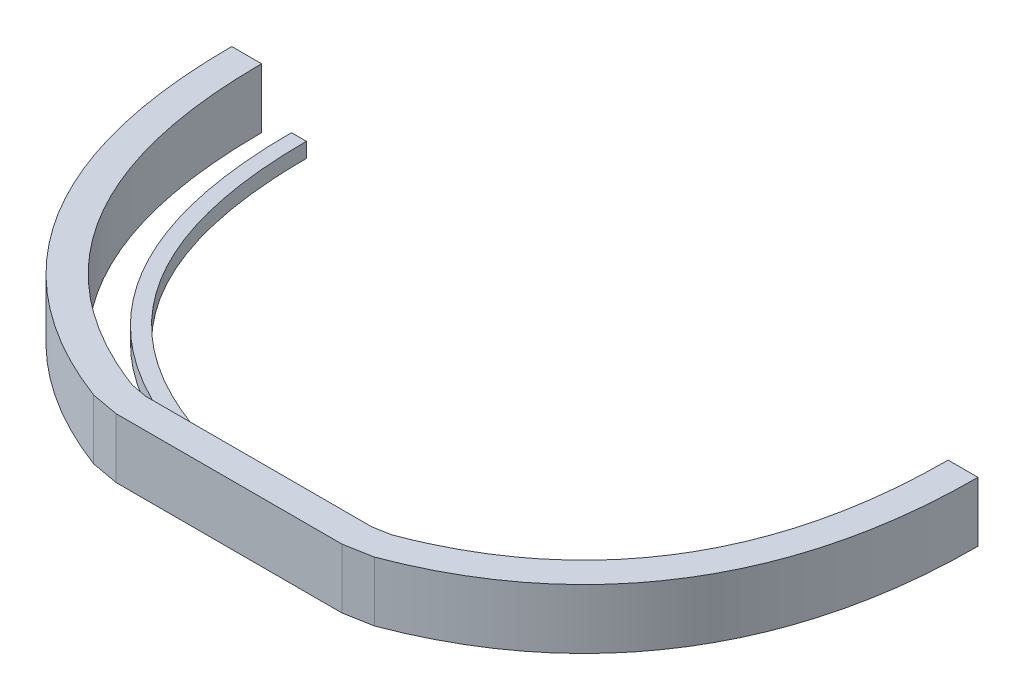
SolidWorks part; units mm, degrees
ref_plane "Front Plane" through (0, 0, 0) normal (0, 0, 1) x (1, 0, 0)
ref_plane "Top Plane" through (0, 0, 0) normal (0, 1, 0) x (1, 0, 0)
ref_plane "Right Plane" through (0, 0, 0) normal (1, 0, 0) x (0, 0, -1)
sketch "Sketch4" plane through (0, 0, -270) normal (0, 1, 0) x (-1, 0, 0)
  line L0 (137.8645, 275) -> (139.9706, 274.6182)
  line L1 (215, 169.1043) -> (225, 169.1044)
  line L2 (-25, 169.1044) -> (-15, 169.1043)
  line L3 (60.0294, 274.6182) -> (62.1355, 275)
  line L5 (62.1355, 285) -> (137.8645, 285)
  line L6 (56.5193, 283.9819) -> (62.1355, 285)
  line L7 (137.8645, 285) -> (143.4807, 283.9819)
  line L8 (62.1355, 275) -> (137.8645, 275)
  line L11 (62.1355, 295) -> (137.8645, 295)
  line L12 (53.0091, 293.3456) -> (62.1355, 295)
  line L13 (-5, 169.1042) -> (0, 169.1041)
  line L14 (137.8645, 295) -> (146.9909, 293.3456)
  line L15 (205, 169.1042) -> (200, 169.1041)
  line L16 (137.8645, 270) -> (138.2155, 269.9364)
  line L17 (61.7845, 269.9364) -> (62.1355, 270)
  line L18 (115.9492, 333.4763) -> (116.336, 333.6697)
  line L19 (62.1355, 270) -> (137.8645, 270)
  line L20 (62.1355, 270) -> (137.8645, 270)
  line L21 (62.1355, 275) -> (137.8645, 275)
  parabola Q8 (200, 169.1041) -> (138.2155, 269.9364) focus (145.0933, 217.5463) apex (175.9662, 244.7858) construction
  parabola Q9 (0, 169.1041) -> (61.7845, 269.9364) focus (54.9067, 217.5463) apex (24.0338, 244.7858) construction
  parabola Q10 (200, 169.1041) -> (138.2155, 269.9364) focus (145.0933, 217.5463) apex (175.9662, 244.7858)
  parabola Q11 (0, 169.1041) -> (61.7845, 269.9364) focus (54.9067, 217.5463) apex (24.0338, 244.7858)
  spline S0 degree 1 poles (-15, 169.1043) (56.5193, 283.9819) knots 0 0 1 1 construction
  spline S1 degree 3 poles (-15, 169.1043) (-15, 170.8319) (-14.9566, 174.3083) (-14.695, 181.0878) (-14.0365, 189.3567) (-12.7038, 198.9137) (-10.1854, 211.1772) (-5.6114, 225.5867) (2.2569, 241.2852) (12.5243, 255.1826) (22.9875, 265.0772) (32.3998, 271.9156) (39.9513, 276.5025) (46.6394, 279.8772) (52.2064, 282.3083) (55.0795, 283.4422) (56.5193, 283.9819) knots 0.497169 0.497169 0.497169 0.497169 0.497311 0.497453 0.497737 0.49802 0.498304 0.498871 0.499439 0.500006 0.500573 0.500857 0.501141 0.501424 0.501566 0.501708 0.501708 0.501708 0.501708
  spline S2 degree 1 poles (215, 169.1043) (143.4807, 283.9819) knots 0 0 1 1 construction
  spline S3 degree 3 poles (215, 169.1043) (215, 170.8319) (214.9566, 174.3083) (214.695, 181.0878) (214.0365, 189.3567) (212.7038, 198.9137) (210.1854, 211.1772) (205.6114, 225.5867) (197.7431, 241.2852) (187.4757, 255.1826) (177.0125, 265.0772) (167.6002, 271.9156) (160.0487, 276.5025) (153.3606, 279.8772) (147.7936, 282.3083) (144.9205, 283.4422) (143.4807, 283.9819) knots 0.497169 0.497169 0.497169 0.497169 0.497311 0.497453 0.497737 0.49802 0.498304 0.498871 0.499439 0.500006 0.500573 0.500857 0.501141 0.501424 0.501566 0.501708 0.501708 0.501708 0.501708
  spline S4 degree 1 poles (-25, 169.1044) (53.0091, 293.3456) knots 0 0 1 1 construction
  spline S5 degree 3 poles (-25, 169.1044) (-25, 170.9167) (-24.9546, 174.5598) (-24.6794, 181.6941) (-23.9842, 190.4326) (-22.5676, 200.5993) (-19.8721, 213.7329) (-14.9305, 229.327) (-6.3218, 246.5207) (4.9983, 261.8482) (16.5376, 272.7565) (26.8613, 280.2554) (35.1038, 285.2608) (42.3596, 288.921) (48.3721, 291.5462) (51.4599, 292.7649) (53.0091, 293.3456) knots 0.497169 0.497169 0.497169 0.497169 0.497311 0.497453 0.497737 0.49802 0.498304 0.498871 0.499439 0.500006 0.500573 0.500857 0.501141 0.501424 0.501566 0.501708 0.501708 0.501708 0.501708
  spline S6 degree 1 poles (225, 169.1044) (146.9909, 293.3456) knots 0 0 1 1 construction
  spline S7 degree 3 poles (225, 169.1044) (225, 170.9167) (224.9546, 174.5598) (224.6794, 181.6941) (223.9842, 190.4326) (222.5676, 200.5993) (219.8721, 213.7329) (214.9305, 229.327) (206.3218, 246.5207) (195.0017, 261.8482) (183.4624, 272.7565) (173.1387, 280.2554) (164.8962, 285.2608) (157.6404, 288.921) (151.6279, 291.5462) (148.5401, 292.7649) (146.9909, 293.3456) knots 0.497169 0.497169 0.497169 0.497169 0.497311 0.497453 0.497737 0.49802 0.498304 0.498871 0.499439 0.500006 0.500573 0.500857 0.501141 0.501424 0.501566 0.501708 0.501708 0.501708 0.501708
  spline S8 degree 1 poles (0, 169.1041) (61.7845, 269.9364) knots 0 0 1 1 construction
  spline S9 degree 3 poles (0, 169.1041) (0, 170.7046) (0.0403, 173.931) (0.2817, 180.1782) (0.8852, 187.7428) (2.092, 196.3852) (4.3447, 207.3437) (8.3672, 219.9761) (15.1249, 233.432) (23.8133, 245.1843) (32.6624, 253.5582) (40.7075, 259.4059) (47.2225, 263.3651) (53.059, 266.3115) (57.958, 268.4514) (60.5089, 269.4582) (61.7845, 269.9364) knots 0.497169 0.497169 0.497169 0.497169 0.497311 0.497453 0.497737 0.49802 0.498304 0.498871 0.499439 0.500006 0.500573 0.500857 0.501141 0.501424 0.501566 0.501708 0.501708 0.501708 0.501708
  spline S10 degree 1 poles (200, 169.1041) (138.2155, 269.9364) knots 0 0 1 1 construction
  spline S11 degree 3 poles (200, 169.1041) (200, 170.7046) (199.9597, 173.931) (199.7183, 180.1782) (199.1148, 187.7428) (197.908, 196.3852) (195.6553, 207.3437) (191.6328, 219.9761) (184.8751, 233.432) (176.1867, 245.1843) (167.3376, 253.5582) (159.2925, 259.4059) (152.7775, 263.3651) (146.941, 266.3115) (142.042, 268.4514) (139.4911, 269.4582) (138.2155, 269.9364) knots 0.497169 0.497169 0.497169 0.497169 0.497311 0.497453 0.497737 0.49802 0.498304 0.498871 0.499439 0.500006 0.500573 0.500857 0.501141 0.501424 0.501566 0.501708 0.501708 0.501708 0.501708
  spline S12 degree 1 poles (-5, 169.1042) (60.0294, 274.6182) knots 0 0 1 1 construction
  spline S13 degree 3 poles (-5, 169.1042) (-5, 170.747) (-4.9587, 174.0568) (-4.7105, 180.4814) (-4.0887, 188.2808) (-2.8399, 197.228) (-0.4987, 208.6216) (3.7076, 221.8463) (10.8355, 236.0497) (20.0503, 248.5171) (29.4374, 257.3979) (37.9383, 263.5758) (44.7987, 267.7443) (50.9191, 270.8334) (56.0408, 273.0704) (58.6991, 274.1195) (60.0294, 274.6182) knots 0.497169 0.497169 0.497169 0.497169 0.497311 0.497453 0.497737 0.49802 0.498304 0.498871 0.499439 0.500006 0.500573 0.500857 0.501141 0.501424 0.501566 0.501708 0.501708 0.501708 0.501708
  spline S14 degree 1 poles (205, 169.1042) (139.9706, 274.6182) knots 0 0 1 1 construction
  spline S15 degree 3 poles (205, 169.1042) (205, 170.747) (204.9587, 174.0568) (204.7105, 180.4814) (204.0887, 188.2808) (202.8399, 197.228) (200.4987, 208.6216) (196.2924, 221.8463) (189.1645, 236.0497) (179.9497, 248.5171) (170.5626, 257.3979) (162.0617, 263.5758) (155.2013, 267.7443) (149.0809, 270.8334) (143.9592, 273.0704) (141.3009, 274.1195) (139.9706, 274.6182) knots 0.497169 0.497169 0.497169 0.497169 0.497311 0.497453 0.497737 0.49802 0.498304 0.498871 0.499439 0.500006 0.500573 0.500857 0.501141 0.501424 0.501566 0.501708 0.501708 0.501708 0.501708
  dimension "D3" = 0
  dimension "D1" = 15
  dimension "D2" = 15
  dimension "D4" = 25
  dimension "D5" = 25
  dimension "D6" = 5
  dimension "D7" = 5
  dimension "D8" = 0
  dimension "D9" = 5
extrude "Boss-Extrude1" add sketch "Sketch4" along normal blind 20 and the other way blind 0.0001 contours L5 L7 S3 L1 S7 L14 L11 L12 S5 L2 S1 L6
extrude "Boss-Extrude4" add sketch "Sketch4<11>" along normal blind 5 separate body contours L15 S15 L0 L8 L3 S13 L13 Q11 L17 L20 L16 Q10 region at (-138.4981, 0, 2.4949)
sketch "Sketch4<11>" plane through (0, 0, -270) normal (0, 1, 0) x (-1, 0, 0) same geometry as "Sketch4"
